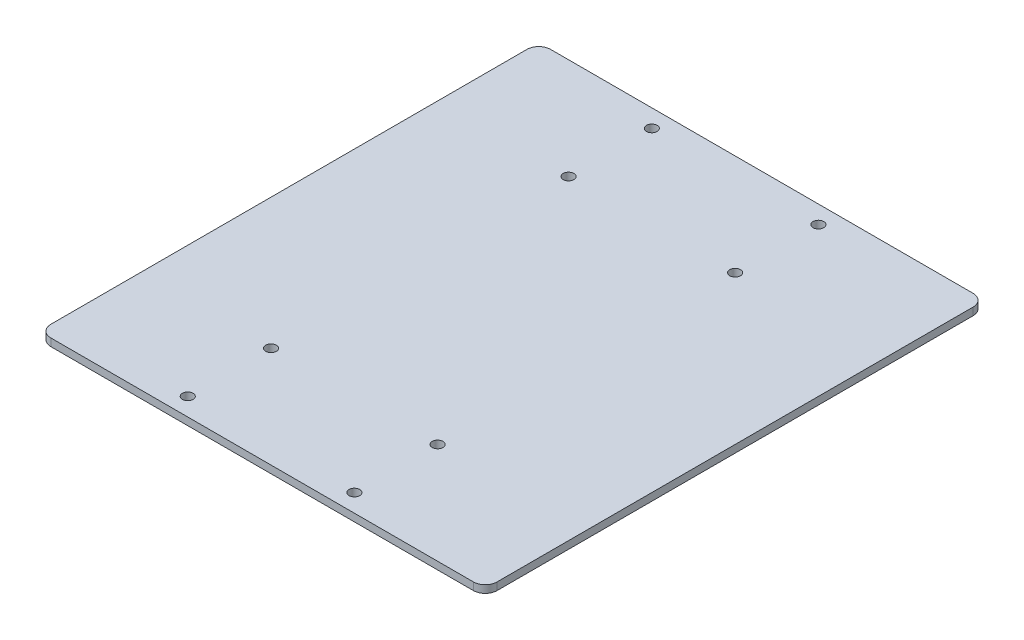
SolidWorks part; units mm, degrees
ref_plane "Front Plane" through (0, 0, 0) normal (0, 0, 1) x (1, 0, 0)
ref_plane "Top Plane" through (0, 0, 0) normal (0, 1, 0) x (1, 0, 0)
ref_plane "Right Plane" through (0, 0, 0) normal (1, 0, 0) x (0, 0, -1)
sketch "Sketch1" plane through (0, 0, 0) normal (0, 1, 0) x (1, 0, 0)
  line L1 (-187.5, -210) -> (187.5, -210)
  line L2 (-187.5, -210) -> (-187.5, 210)
  line L3 (-187.5, 210) -> (187.5, 210)
  line L4 (187.5, -210) -> (187.5, 210)
  line L5 (-187.5, -210) -> (187.5, 210) construction
  line L6 (-187.5, 210) -> (187.5, -210) construction
  point P0 (0, 0)
  dimension "D1" = 375
  dimension "D2" = 420
extrude "Boss-Extrude1" add sketch "Sketch1" along normal blind 6.35
fillet "Fillet1" radius 10 4 edges at (-187.5, 3.175, -210) (187.5, 3.175, -210) (187.5, 3.175, 210) (-187.5, 3.175, 210)
hole_wizard "M8 Clearance Hole1" positions "Sketch2" profile "Sketch3" hole size "M8" standard "ANSI Metric" end condition through all
sketch "Sketch2" plane through (0, 6.35, 0) normal (0, 1, 0) x (1, 0, 0)
  line L1 (-77.5, -195) -> (62.5, -195)
  line L2 (-77.5, -195) -> (-77.5, -125)
  line L3 (-77.5, -125) -> (62.5, -125)
  line L4 (62.5, -195) -> (62.5, -125)
  line L5 (-177.5, -210) -> (177.5, -210) construction
  line L6 (-187.5, 200) -> (-187.5, -200) construction
  point P1 (-77.5, -195)
  point P2 (62.5, -125)
  point P45 (-77.5, -125)
  point P46 (62.5, -195)
  dimension "D1" = 140
  dimension "D2" = 70
  dimension "D3" = 15
  dimension "D4" = 110
sketch "Sketch3" plane through (-77.5, 6.35, 195) normal (1, 0, 0) x (0, 0, 1)
  line L0 (0, 0) -> (0, 6.35)
  line L1 (0, 6.35) -> (4.5, 6.35)
  line L2 (4.5, 6.35) -> (4.5, 0)
  line L5 (4.5, 0) -> (0, 0)
  line L11 (0, -6.35) -> (0, 107.95) construction
  dimension "Thru Hole Dia." = 9
  dimension "Thru Hole Depth" = 6.35
mirror "Mirror1" about plane through (0, 0, 0) normal (0, 0, 1) of "M8 Clearance Hole1"
